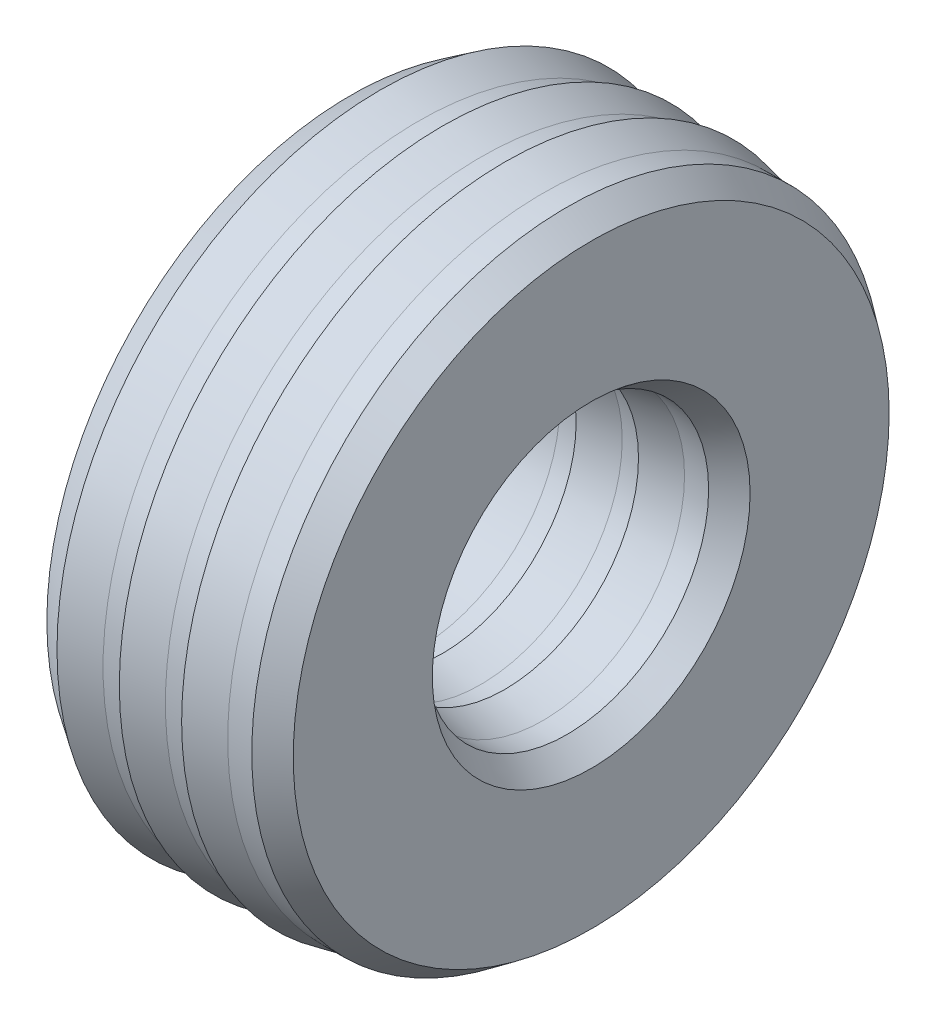
SolidWorks part; units mm, degrees
ref_plane "Front Plane" through (0, 0, 0) normal (0, 0, 1) x (1, 0, 0)
ref_plane "Top Plane" through (0, 0, 0) normal (0, 1, 0) x (1, 0, 0)
ref_plane "Right Plane" through (0, 0, 0) normal (1, 0, 0) x (0, 0, -1)
sketch "Sketch6" plane through (0, 0, 0) normal (0, 0, 1) x (1, 0, 0)
  line L0 (0, 0) -> (0, 1.4478) construction
  line L1 (-1.2319, 3.2258) -> (1.2319, 3.2258)
  line L2 (-1.2319, 3.2258) -> (-1.2319, 1.4478)
  line L3 (-1.2319, 1.4478) -> (1.2319, 1.4478)
  line L4 (1.2319, 3.2258) -> (1.2319, 1.4478)
  line L5 (0, 0) -> (1.2319, 0) construction
  line L6 (0, 0) -> (-1.2319, 0) construction
  line L7 (0, 0) -> (0, -3.2258) construction
  line L8 (-1.2827, -3.2258) -> (1.2827, -3.2258) construction
  dimension "Width" = 2.4638
  dimension "ID" = 2.8956
  dimension "OD" = 6.4516
  dimension "D1" = 1.778
  dimension "D2" = 3.2258
  dimension "Groove Width" = 2.5654
sketch "Sketch7" plane through (0, 0, 0) normal (0, 0, 1) x (1, 0, 0)
  line L0 (0, 1.4478) -> (0, 3.2258) construction
  line L1 (-1.2319, 3.2258) -> (1.2319, 3.2258) construction
  line L2 (-0.9271, 2.7413) -> (-0.6223, 2.7413)
  line L3 (-0.9271, 1.9323) -> (-0.6223, 1.9323)
  line L4 (-1.2319, 3.2258) -> (-1.2319, 1.4478) construction
  line L5 (-1.2319, 2.7413) -> (-1.2319, 1.9323) construction
  line L6 (-1.2319, 2.3368) -> (0, 2.3368) construction
  line L7 (-0.6223, 2.7413) -> (-0.6223, 2.9591)
  line L8 (-0.6223, 2.9591) -> (0.6223, 2.9591)
  line L9 (0.6223, 2.9591) -> (0.6223, 1.7145)
  line L10 (0.6223, 1.7145) -> (-0.6223, 1.7145)
  line L11 (-0.6223, 1.7145) -> (-0.6223, 1.9323)
  line L12 (-1.2319, 2.8624) -> (-1.2319, 3.1047)
  line L13 (-0.5359, 3.2258) -> (-0.2896, 3.2258)
  line L14 (1.2319, 3.048) -> (1.2319, 1.6256)
  line L15 (0.9855, 1.4478) -> (0.7391, 1.4478)
  line L16 (-1.2319, 1.5689) -> (-1.2319, 1.8112)
  line L17 (0.9855, 3.2258) -> (1.2319, 3.048)
  line L18 (1.2319, 1.6256) -> (0.9855, 1.4478)
  line L19 (0.6223, 2.3368) -> (1.2319, 2.3368) construction
  line L20 (1.2319, 3.2258) -> (1.2319, 1.4478) construction
  line L21 (-0.6223, 2.9591) -> (-1.2319, 2.9591) construction
  line L22 (-0.9271, 2.9591) -> (-0.9271, 1.9323) construction
  line L23 (-0.9271, 2.7413) -> (-1.2319, 2.8624)
  line L24 (-1.2319, 3.1047) -> (-0.9271, 3.3058)
  line L25 (-0.9271, 3.3058) -> (-0.5359, 3.2258)
  line L26 (-0.2896, 3.2258) -> (-0.2896, 3.3058)
  line L27 (-0.2896, 3.3058) -> (0.1016, 3.2258)
  line L28 (0.348, 3.2258) -> (0.348, 3.3058)
  line L29 (0.348, 3.3058) -> (0.7391, 3.2258)
  line L30 (0.1016, 3.2258) -> (0.348, 3.2258)
  line L31 (0.7391, 3.2258) -> (0.9855, 3.2258)
  line L32 (-0.9271, 1.9323) -> (-1.2319, 1.8112)
  line L33 (-1.2319, 1.5689) -> (-0.9271, 1.3678)
  line L35 (-1.2319, 1.4478) -> (1.2319, 1.4478) construction
  line L36 (-0.9271, 1.3678) -> (-0.5359, 1.4478)
  line L37 (-0.2896, 1.4478) -> (-0.2896, 1.3678)
  line L38 (-0.2896, 1.3678) -> (0.1016, 1.4478)
  line L39 (0.348, 1.4478) -> (0.348, 1.3678)
  line L40 (0.348, 1.3678) -> (0.7391, 1.4478)
  line L41 (0.348, 1.4478) -> (0.1016, 1.4478)
  line L42 (-0.2896, 1.4478) -> (-0.5359, 1.4478)
  circle A0 centre (0, 2.3368) radius 0.6223 construction
  dimension "D1" = 1.2446
  dimension "D2" = 0.809
  dimension "D3" = 1.4224
  dimension "D4" = 2.2174
  dimension "D6" = 0.1211
  dimension "D8" = 1.938
  dimension "D5" = 0.4845
  dimension "D7" = 0.1211
  dimension "D9" = 0.2464
revolve "Revolve1" add sketch "Sketch7" angle 360 about L5
sketch "Sketch5" plane through (0, 0, 0) normal (0, 0, 1) x (1, 0, 0)
  circle A0 centre (0, 2.3368) radius 0.6223
  circle A4 centre (0, 2.3368) radius 0.6223 construction
  point P2 (0, 28.194)
  point P7 (0, 1.7145)
  point P8 (0, 2.9591)
  point P9 (0, 2.3368)
sketch "Sketch8" plane through (0, 0, 0) normal (1, 0, 0) x (0, 0, -1)
  line L0 (-2.0924, 2.0924) -> (-1.2123, 1.2123) construction
  line L1 (2.0924, 2.0924) -> (1.2123, 1.2123) construction
  circle A0 centre (0, 0) radius 1.7145 construction
  arc A1 (1.6524, 1.6524) -> (-1.6524, 1.6524) centre (0, 0) ccw
  circle A2 centre (0, 0) radius 2.9591 construction
  dimension "D1" = 90
ref_plane "Plane2" through (0, 0, 0) normal (0, 0.7071, -0.7071) x (1, 0, 0)
sketch "Sketch9" plane through (0, 0, 0) normal (0, 0.7071, -0.7071) x (1, 0, 0)
  line L0 (0, -2.9591) -> (0, -1.7145) construction
  line L1 (0.6223, -2.3368) -> (-0.6223, -2.3368) construction
  line L2 (0, -1.9685) -> (0, -2.3368)
  circle A0 centre (0, -2.3368) radius 0.6223 construction
  circle A1 centre (0, -1.8415) radius 0.127 construction
  dimension "D1" = 0.254
surface "Surface-Sweep4" parameters "D1"=2160
sketch3d "3DSketch2"
  spline S0 degree 3 poles (732.55, 407.6333, 547.5874) (-44.4443, 13.4873, 9.0339) (-0.9079, -1.1508, 0.0524) (0.3956, 1.7504, 1.5375) (0.3627, 1.9019, 1.6153) (0.1582, 2.114, 1.6793) (-0.0073, 2.1689, 1.6625) (-0.2746, 2.1322, 1.5261) (-0.3683, 2.0423, 1.41) (-0.3683, 1.8442, 1.1857) (-0.2746, 1.7434, 1.0825) (-0.0073, 1.682, 0.9696) (0.1582, 1.7252, 0.9601) (0.3627, 1.9377, 0.9966) (0.3956, 2.102, 1.0384) (0.2849, 2.3783, 1.0793) (0.1446, 2.4825, 1.0755) (-0.1446, 2.5164, 0.9937) (-0.2849, 2.4453, 0.9173) (-0.3956, 2.2209, 0.751) (-0.3627, 2.0751, 0.6644) (-0.1582, 1.8991, 0.5401) (0.0073, 1.8752, 0.5029) (0.2746, 1.9984, 0.4665) (0.3683, 2.1427, 0.4648) (0.3683, 2.4413, 0.4462) (0.2746, 2.587, 0.4277) (0.0073, 2.7093, 0.3573) (-0.1582, 2.6824, 0.3067) (-0.3627, 2.4871, 0.2021) (-0.3956, 2.3249, 0.1501) (-0.2849, 2.0615, 0.0653) (-0.1446, 1.9685, 0.0322) (0.1446, 1.9685, -0.0322) (0.2849, 2.0615, -0.0653) (0.3956, 2.3249, -0.1501) (0.3627, 2.4871, -0.2021) (0.1582, 2.6824, -0.3067) (-0.0073, 2.7093, -0.3573) (-0.2746, 2.587, -0.4277) (-0.3683, 2.4413, -0.4462) (-0.3683, 2.1427, -0.4648) (-0.2746, 1.9984, -0.4665) (-0.0073, 1.8752, -0.5029) (0.1582, 1.8991, -0.5401) (0.3627, 2.0751, -0.6644) (0.3956, 2.2209, -0.751) (0.2849, 2.4453, -0.9173) (0.1446, 2.5164, -0.9937) (-0.1446, 2.4825, -1.0755) (-0.2849, 2.3783, -1.0793) (-0.3956, 2.102, -1.0384) (-0.3627, 1.9377, -0.9966) (-0.1582, 1.7252, -0.9601) (0.0073, 1.682, -0.9696) (0.2746, 1.7434, -1.0825) (0.3683, 1.8442, -1.1857) (0.3683, 2.0423, -1.41) (0.2746, 2.1322, -1.5261) (0.0073, 2.1689, -1.6625) (-0.1582, 2.114, -1.6793) (-0.3627, 1.9019, -1.6153) (-0.3956, 1.7504, -1.5375) (0.9079, -1.1507, -0.0525) (44.4437, 13.4871, -9.0338) (-732.5321, 407.6242, -547.575) knots -0.673489 -0.673489 -0.673489 -0.673489 0.03125 0.03125 0.0625 0.0625 0.09375 0.09375 0.125 0.125 0.15625 0.15625 0.1875 0.1875 0.21875 0.21875 0.25 0.25 0.28125 0.28125 0.3125 0.3125 0.34375 0.34375 0.375 0.375 0.40625 0.40625 0.4375 0.4375 0.46875 0.46875 0.5 0.5 0.53125 0.53125 0.5625 0.5625 0.59375 0.59375 0.625 0.625 0.65625 0.65625 0.6875 0.6875 0.71875 0.71875 0.75 0.75 0.78125 0.78125 0.8125 0.8125 0.84375 0.84375 0.875 0.875 0.90625 0.90625 0.9375 0.9375 0.96875 0.96875 1.673484 1.673484 1.673484 1.673484 only from (0, 1.3919, 1.3919) to (0, 1.3919, -1.3919) construction
  spline S1 degree 3 poles (0, 1.3919, 1.3919) (0.1464, 1.4151, 1.3688) (0.2849, 1.504, 1.4114) (0.3956, 1.7504, 1.5375) (0.3627, 1.9019, 1.6153) (0.1582, 2.114, 1.6793) (-0.0073, 2.1689, 1.6625) (-0.2746, 2.1322, 1.5261) (-0.3683, 2.0423, 1.41) (-0.3683, 1.8442, 1.1857) (-0.2746, 1.7434, 1.0825) (-0.0073, 1.682, 0.9696) (0.1582, 1.7252, 0.9601) (0.3627, 1.9377, 0.9966) (0.3956, 2.102, 1.0384) (0.2849, 2.3783, 1.0793) (0.1446, 2.4825, 1.0755) (-0.1446, 2.5164, 0.9937) (-0.2849, 2.4453, 0.9173) (-0.3956, 2.2209, 0.751) (-0.3627, 2.0751, 0.6644) (-0.1582, 1.8991, 0.5401) (0.0073, 1.8752, 0.5029) (0.2746, 1.9984, 0.4665) (0.3683, 2.1427, 0.4648) (0.3683, 2.4413, 0.4462) (0.2746, 2.587, 0.4277) (0.0073, 2.7093, 0.3573) (-0.1582, 2.6824, 0.3067) (-0.3627, 2.4871, 0.2021) (-0.3956, 2.3249, 0.1501) (-0.2849, 2.0615, 0.0653) (-0.1446, 1.9685, 0.0322) (0.1446, 1.9685, -0.0322) (0.2849, 2.0615, -0.0653) (0.3956, 2.3249, -0.1501) (0.3627, 2.4871, -0.2021) (0.1582, 2.6824, -0.3067) (-0.0073, 2.7093, -0.3573) (-0.2746, 2.587, -0.4277) (-0.3683, 2.4413, -0.4462) (-0.3683, 2.1427, -0.4648) (-0.2746, 1.9984, -0.4665) (-0.0073, 1.8752, -0.5029) (0.1582, 1.8991, -0.5401) (0.3627, 2.0751, -0.6644) (0.3956, 2.2209, -0.751) (0.2849, 2.4453, -0.9173) (0.1446, 2.5164, -0.9937) (-0.1446, 2.4825, -1.0755) (-0.2849, 2.3783, -1.0793) (-0.3956, 2.102, -1.0384) (-0.3627, 1.9377, -0.9966) (-0.1582, 1.7252, -0.9601) (0.0073, 1.682, -0.9696) (0.2746, 1.7434, -1.0825) (0.3683, 1.8442, -1.1857) (0.3683, 2.0423, -1.41) (0.2746, 2.1322, -1.5261) (0.0073, 2.1689, -1.6625) (-0.1582, 2.114, -1.6793) (-0.3627, 1.9019, -1.6153) (-0.3956, 1.7504, -1.5375) (-0.2849, 1.504, -1.4114) (-0.1464, 1.4151, -1.3688) (0, 1.3919, -1.3919) knots 0 0 0 0 0.03125 0.03125 0.0625 0.0625 0.09375 0.09375 0.125 0.125 0.15625 0.15625 0.1875 0.1875 0.21875 0.21875 0.25 0.25 0.28125 0.28125 0.3125 0.3125 0.34375 0.34375 0.375 0.375 0.40625 0.40625 0.4375 0.4375 0.46875 0.46875 0.5 0.5 0.53125 0.53125 0.5625 0.5625 0.59375 0.59375 0.625 0.625 0.65625 0.65625 0.6875 0.6875 0.71875 0.71875 0.75 0.75 0.78125 0.78125 0.8125 0.8125 0.84375 0.84375 0.875 0.875 0.90625 0.90625 0.9375 0.9375 0.96875 0.96875 1 1 1 1
sketch "Sketch10" plane through (0, 0, 0) normal (1, 0, 0) x (0, 0, -1)
  circle A0 centre (-1.3021, 1.3021) radius 0.127
delete or keep bodies "Body-Delete2" type delete bodies bodies 119
sweep "Sweep2" add profiles "Sketch10" path "3DSketch2"
ref_axis "Axis1" through (-1.3551, 0, 0) along (1, 0, 0)
pattern_circular "CirPattern2" count 4 over 360 about axis through (-1.3551, 0, 0) along (1, 0, 0) of bodies 120
equation "\"D1@Sketch7\"=\"D1@Sketch6\"*.7"
equation "\"D2@Sketch7\"=\"D1@Sketch7\"*.65"
equation "\"D3@Sketch7\"=\"D1@Sketch6\"*.8"
equation "\"D4@Sketch7\"=\"Width@Sketch6\"*.9"
equation "\"D6@Sketch7\"=\"D5@Sketch7\"/4"
equation "\"D7@Sketch7\"=\"D6@Sketch7\""
equation "\"D8@Sketch7\"=\"D1@Sketch6\"*1.09"
equation "\"D9@Sketch7\"=\"Width@Sketch6\"/10"
equation "\"D2@Sketch6\"=\"OD@Sketch6\"/2"
